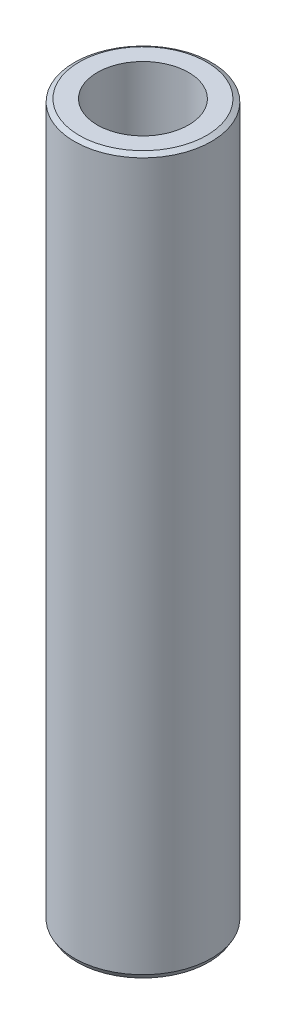
SolidWorks part; units mm, degrees
ref_plane "Front Plane" through (0, 0, 0) normal (0, 0, 1) x (1, 0, 0)
ref_plane "Top Plane" through (0, 0, 0) normal (0, 1, 0) x (1, 0, 0)
ref_plane "Right Plane" through (0, 0, 0) normal (1, 0, 0) x (0, 0, -1)
sketch "Sketch1" plane through (0, 0, 0) normal (0, 1, 0) x (1, 0, 0)
  circle A0 centre (0, 0) radius 57.5
  dimension "SHAFT_OD" = 115
extrude "Boss-Extrude1" add sketch "Sketch1" along normal blind 600
sketch "Sketch2" plane through (0, 0, 0) normal (0, 1, 0) x (1, 0, 0)
  circle A0 centre (0, 0) radius 38.2694
  dimension "BORE_D" = 76.5388
extrude "Cut-Extrude1" cut sketch "Sketch2" along normal through all
chamfer "Chamfer1" distance 2.3482 angle 60 2 edges at (0, 600, 57.5) (0, 0, 57.5) first distance on face at (0, 600, 57.5) first distance on face at (0, 0, 38.2694)
